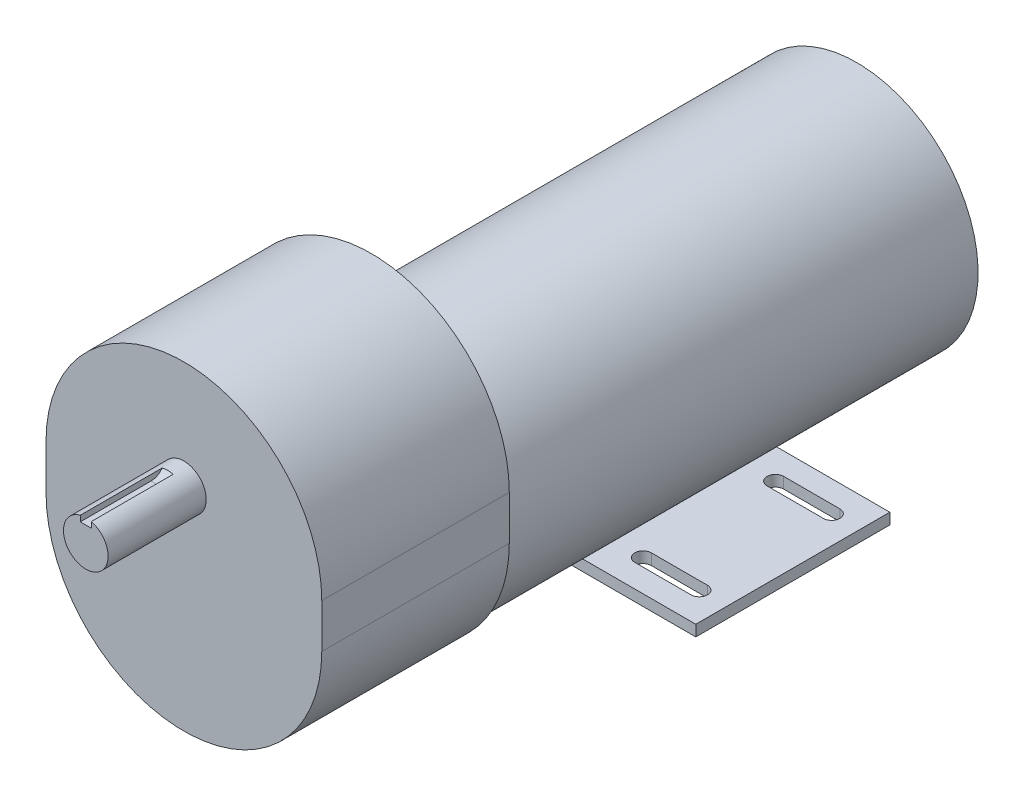
SolidWorks part; units mm, degrees
ref_plane "Front Plane" through (0, 0, 0) normal (0, 0, 1) x (1, 0, 0)
ref_plane "Top Plane" through (0, 0, 0) normal (0, 1, 0) x (1, 0, 0)
ref_plane "Right Plane" through (0, 0, 0) normal (1, 0, 0) x (0, 0, -1)
sketch "Sketch1" plane through (0, 0, 0) normal (0, 0, 1) x (1, 0, 0)
  circle A0 centre (0, 0) radius 12.846
  dimension "D1" = 25.6921
extrude "Boss-Extrude1" add sketch "Sketch1" against normal blind 56.4642
sketch "Sketch2" plane through (0, 0, -56.4642) normal (0, 0, -1) x (-1, 0, 0)
  line L0 (0, -17.0878) -> (0, -42.4878) construction
  line L1 (79.375, -17.0878) -> (79.375, -42.4878)
  line L2 (-79.375, -17.0878) -> (-79.375, -42.4879)
  arc A0 (79.375, -17.0878) -> (-79.375, -17.0878) centre (0, -17.0878) ccw
  arc A1 (-79.375, -42.4879) -> (79.375, -42.4878) centre (0, -42.4878) ccw
  point P3 (0, -29.7878)
  point P8 (0, -121.8628)
  point P9 (0, 62.2872)
  dimension "D1" = 158.75
  dimension "D2" = 184.15
  dimension "D3" = 121.8628
extrude "Boss-Extrude2" add sketch "Sketch2" along normal blind 107.95
sketch "Sketch3" plane through (0, 0, -164.4142) normal (0, 0, -1) x (-1, 0, 0)
  circle A0 centre (0, -52.0129) radius 69.85
  arc A1 (-79.375, -42.4878) -> (79.375, -42.4878) centre (0, -42.4878) ccw construction
  point P5 (0, -121.8628)
  dimension "D1" = 139.7
extrude "Boss-Extrude3" add sketch "Sketch3" along normal blind 279.4
sketch "Sketch4" plane through (0, 0, 0) normal (0, 0, 1) x (1, 0, 0)
  line L0 (-3.1623, 12.4507) -> (-3.1623, 9.1487)
  line L1 (-3.1623, 9.1487) -> (3.1623, 9.1487)
  line L2 (3.1623, 9.1487) -> (3.1623, 12.4507)
  circle A0 centre (0, 0) radius 12.846 construction
  arc A1 (-3.1623, 12.4507) -> (3.1623, 12.4507) centre (0, 0) cw
  point P4 (0, 9.1487)
  dimension "D1" = 6.3246
  dimension "D2" = 3.302
extrude "Cut-Extrude1" cut sketch "Sketch4" against normal blind 47.1297 contours L1 L2 A1 L0
fillet "Fillet1" radius 7.62 1 edges at (0, 9.1487, -47.1297)
sketch "Sketch5" plane through (0, 0, 0) normal (0, 1, 0) x (1, 0, 0)
  line L0 (69.85, 443.8142) -> (-69.85, 443.8142) construction
  line L1 (-82.55, 380.3142) -> (82.55, 380.3142)
  line L2 (-82.55, 380.3142) -> (-82.55, 268.6126)
  line L3 (-82.55, 268.6126) -> (82.55, 268.6126)
  line L4 (82.55, 380.3142) -> (82.55, 268.6126)
  line L5 (0, -101.2825) -> (0, 101.2825) construction
  point P6 (0, 268.6126)
  dimension "D1" = 63.5
  dimension "D2" = 165.1
  dimension "D3" = 0
extrude "Plate Extrude" add sketch "Sketch5" along normal blind 6.35 from offset 139.7 separate body offset against normal yes
sketch "Sketch6" plane through (0, -139.7, 0) normal (0, -1, 0) x (1, 0, 0)
  line L0 (-66.5069, -362.8517) -> (-34.1278, -362.8517) construction
  line L1 (-66.5069, -358.0892) -> (-34.1278, -358.0892)
  line L2 (-66.5069, -367.6142) -> (-34.1278, -367.6142)
  line L3 (82.55, -380.3142) -> (-82.55, -380.3142) construction
  line L4 (-66.5069, -286.6517) -> (-34.1278, -286.6517) construction
  line L5 (-66.5069, -281.8892) -> (-34.1278, -281.8892)
  line L6 (-66.5069, -291.4142) -> (-34.1278, -291.4142)
  arc A0 (-66.5069, -358.0892) -> (-66.5069, -367.6142) centre (-66.5069, -362.8517) ccw
  arc A1 (-34.1278, -367.6142) -> (-34.1278, -358.0892) centre (-34.1278, -362.8517) ccw
  arc A2 (-66.5069, -281.8892) -> (-66.5069, -291.4142) centre (-66.5069, -286.6517) ccw
  arc A3 (-34.1278, -291.4142) -> (-34.1278, -281.8892) centre (-34.1278, -286.6517) ccw
  point P2 (-50.3174, -362.8517)
  point P9 (-71.2694, -362.8517)
  point P12 (-50.3174, -286.6517)
  point P17 (-66.5069, -284.2595)
  point P18 (-34.1278, -284.2842)
  dimension "D1" = 12.7
  dimension "D2" = 4.7625
  dimension "D3" = 76.2
  dimension "D4" = 9.525
extrude "Slot Cut" cut sketch "Sketch6" against normal blind 6.35
mirror "Mirror Slot Cut" about plane through (0, 0, 0) normal (1, 0, 0) of "Slot Cut"
